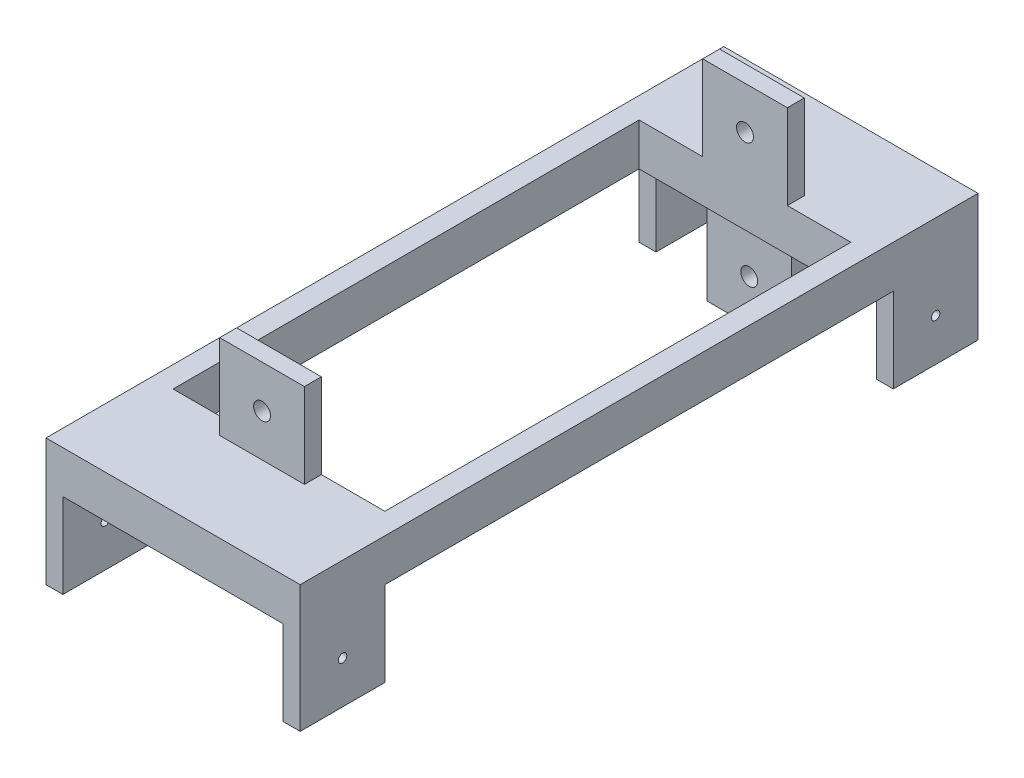
SolidWorks part; units mm, degrees
ref_plane "Front Plane" through (0, 0, 0) normal (0, 0, 1) x (1, 0, 0)
ref_plane "Top Plane" through (0, 0, 0) normal (0, 1, 0) x (1, 0, 0)
ref_plane "Right Plane" through (0, 0, 0) normal (1, 0, 0) x (0, 0, -1)
sketch "Sketch1" plane through (0, 0, 0) normal (0, 1, 0) x (1, 0, 0)
  line L1 (-15, 40) -> (15, 40)
  line L2 (-15, 40) -> (-15, -40)
  line L3 (-15, -40) -> (15, -40)
  line L4 (15, 40) -> (15, -40)
  line L5 (-15, 40) -> (15, -40) construction
  line L6 (-15, -40) -> (15, 40) construction
  point P0 (0, 0)
  dimension "D1" = 30
  dimension "D2" = 80
extrude "Boss-Extrude1" add sketch "Sketch1" along normal blind 5
sketch "Sketch2" plane through (15, 0, 0) normal (1, 0, 0) x (0, 0, -1)
  line L1 (-40, 0) -> (-30, 0)
  line L2 (-40, 0) -> (-40, -10)
  line L3 (-40, -10) -> (-30, -10)
  line L4 (-30, 0) -> (-30, -10)
  line L5 (40, 0) -> (30, 0)
  line L6 (40, 0) -> (40, -10)
  line L7 (40, -10) -> (30, -10)
  line L8 (30, 0) -> (30, -10)
  dimension "D1" = 10
  dimension "D2" = 10
  dimension "D3" = 10
  dimension "D4" = 10
extrude "Boss-Extrude2" add sketch "Sketch2" against normal blind 30
sketch "Sketch3" plane through (15, 0, 0) normal (1, 0, 0) x (0, 0, -1)
  line L0 (-40, 5) -> (-40, -10) construction
  line L2 (-40, -10) -> (-30, -10) construction
  line L3 (30, -10) -> (40, -10) construction
  line L4 (30, 0) -> (30, -10) construction
  circle A0 centre (-35, -5) radius 0.5
  circle A1 centre (35, -5) radius 0.5
  dimension "D1" = 1
  dimension "D2" = 1
  dimension "D3" = 5
  dimension "D4" = 5
  dimension "D5" = 5
  dimension "D6" = 5
extrude "Cut-Extrude1" cut sketch "Sketch3" against normal through all both and the other way through all
sketch "Sketch4" plane through (0, 5, 0) normal (0, 1, 0) x (1, 0, 0)
  line L9 (-12.5, -27.5) -> (12.5, -27.5)
  line L10 (-12.5, -27.5) -> (-12.5, 27.5)
  line L11 (-12.5, 27.5) -> (12.5, 27.5)
  line L12 (12.5, -27.5) -> (12.5, 27.5)
  line L13 (-12.5, -27.5) -> (12.5, 27.5) construction
  line L14 (-12.5, 27.5) -> (12.5, -27.5) construction
  point P0 (0, 0)
  dimension "D1" = 55
  dimension "D2" = 25
extrude "Cut-Extrude2" cut sketch "Sketch4" against normal through all both and the other way through all
sketch "Sketch5" plane through (0, 0, -40) normal (0, 0, -1) x (-1, 0, 0)
  line L0 (15, -10) -> (-15, -10) construction
  line L1 (-13, -10) -> (13, -10)
  line L2 (-13, -10) -> (-13, 0)
  line L3 (-13, 0) -> (13, 0)
  line L4 (13, -10) -> (13, 0)
  line L5 (-15, 5) -> (-15, -10) construction
  line L6 (15, 5) -> (15, -10) construction
  dimension "D1" = 10
  dimension "D2" = 2
  dimension "D3" = 2
extrude "Cut-Extrude3" cut sketch "Sketch5" against normal through all both and the other way through all
sketch "Sketch6" plane through (0, 0, -40) normal (0, 0, -1) x (-1, 0, 0)
  line L0 (-13, 0) -> (13, 0) construction
  line L1 (-5, 0) -> (5, 0)
  line L2 (-5, 0) -> (-5, -10)
  line L3 (-5, -10) -> (5, -10)
  line L4 (5, 0) -> (5, -10)
  line L6 (-13, -10) -> (-13, 0) construction
  line L7 (13, 0) -> (13, -10) construction
  dimension "D1" = 8
  dimension "D2" = 10
  dimension "D3" = 8
extrude "Boss-Extrude3" add sketch "Sketch6" against normal blind 80
sketch "Sketch7" plane through (0, 0, -40) normal (0, 0, -1) x (-1, 0, 0)
  line L0 (-5, 0) -> (-5, -10) construction
  line L1 (-5, -10) -> (5, -10) construction
  circle A0 centre (0, -5) radius 1
  point P4 (-5, -5)
  dimension "D1" = 2
  dimension "D2" = 5
  dimension "D3" = 5
extrude "Cut-Extrude4" cut sketch "Sketch7" against normal through all both and the other way through all
sketch "Sketch8" plane through (5, 0, 0) normal (1, 0, 0) x (0, 0, -1)
  line L0 (-40, -10) -> (40, -10) construction
  line L1 (-28, -10) -> (28, -10)
  line L2 (-28, -10) -> (-28, 0)
  line L3 (-28, 0) -> (28, 0)
  line L4 (28, -10) -> (28, 0)
  line L5 (-27.5, 0) -> (27.5, 0) construction
  line L6 (-30, -10) -> (-30, 0) construction
  line L7 (30, 0) -> (30, -10) construction
  dimension "D1" = 2
  dimension "D2" = 2
extrude "Cut-Extrude5" cut sketch "Sketch8" against normal through all both and the other way through all
sketch "Sketch9" plane through (0, 0, 40) normal (0, 0, 1) x (1, 0, 0)
  line L1 (-5, -10) -> (5, -10)
  line L2 (-5, -10) -> (-5, 0)
  line L3 (-5, 0) -> (5, 0)
  line L4 (5, -10) -> (5, 0)
extrude "Cut-Extrude6" cut sketch "Sketch9" against normal blind 10
sketch "Sketch10" plane through (0, 0, -40) normal (0, 0, -1) x (-1, 0, 0)
  line L1 (-5, -10) -> (5, -10)
  line L2 (-5, -10) -> (-5, 0)
  line L3 (-5, 0) -> (5, 0)
  line L4 (5, -10) -> (5, 0)
extrude "Cut-Extrude7" cut sketch "Sketch10" against normal blind 10
sketch "Sketch12" plane through (0, 5, 0) normal (0, 1, 0) x (1, 0, 0)
  line L0 (-12.5, -27.5) -> (12.5, -27.5) construction
  line L1 (-5, -27.5) -> (5, -27.5)
  line L2 (-5, -27.5) -> (-5, -29.5)
  line L3 (-5, -29.5) -> (5, -29.5)
  line L4 (5, -27.5) -> (5, -29.5)
  line L5 (12.5, 27.5) -> (-12.5, 27.5) construction
  line L6 (5, 27.5) -> (-5, 27.5)
  line L7 (5, 27.5) -> (5, 29.5)
  line L8 (5, 29.5) -> (-5, 29.5)
  line L9 (-5, 27.5) -> (-5, 29.5)
  line L10 (15, -40) -> (15, 40) construction
  dimension "D1" = 2
  dimension "D2" = 10
  dimension "D3" = 10
  dimension "D4" = 2
  dimension "D5" = 10
  dimension "D6" = 10
extrude "Boss-Extrude5" add sketch "Sketch12" along normal blind 10
sketch "Sketch13" plane through (0, 0, 29.5) normal (0, 0, 1) x (1, 0, 0)
  line L0 (-5, 15) -> (-5, 5) construction
  line L1 (-5, 5) -> (5, 5) construction
  circle A0 centre (0, 10) radius 1
  dimension "D1" = 2
  dimension "D2" = 5
  dimension "D3" = 5
extrude "Cut-Extrude8" cut sketch "Sketch13" against normal through all both and the other way through all contours A0
